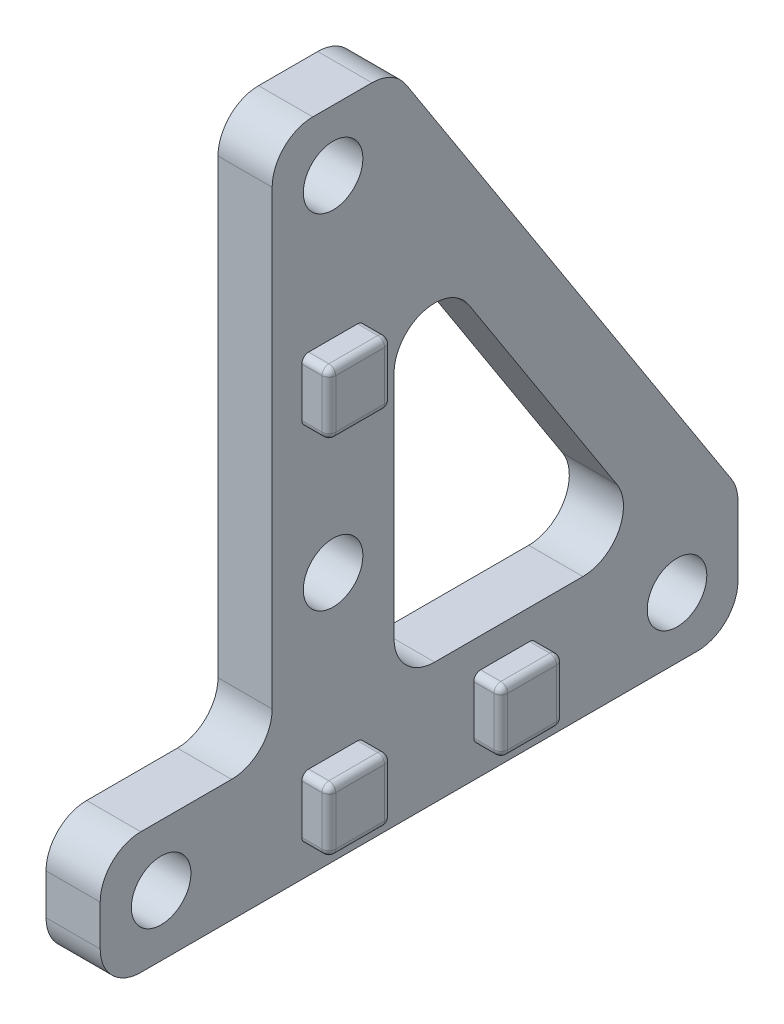
SolidWorks part; units mm, degrees
ref_plane "Front Plane" through (0, 0, 0) normal (0, 0, 1) x (1, 0, 0)
ref_plane "Top Plane" through (0, 0, 0) normal (0, 1, 0) x (1, 0, 0)
ref_plane "Right Plane" through (0, 0, 0) normal (1, 0, 0) x (0, 0, -1)
sketch "Sketch1" plane through (0, 0, 0) normal (1, 0, 0) x (0, 0, -1)
  line L0 (-4.5, 4.5) -> (-17.2, 4.5)
  line L1 (-17.2, 4.5) -> (-17.2, -4.5)
  line L2 (-17.2, -4.5) -> (29.9, -4.5)
  line L3 (29.9, -4.5) -> (29.9, 4.5)
  line L4 (29.9, 4.5) -> (4.5, 43.87)
  line L5 (4.5, 43.87) -> (-4.5, 43.87)
  line L6 (-4.5, 43.87) -> (-4.5, 4.5)
  line L7 (4.5, 4.5) -> (23.9497, 4.5)
  line L8 (23.9497, 4.5) -> (4.5, 34.6471)
  line L9 (4.5, 34.6471) -> (4.5, 4.5)
  circle A1 centre (25.4, 0) radius 2.2
  circle A2 centre (0, 13.97) radius 2.2
  circle A3 centre (0, 39.37) radius 2.2
  circle A4 centre (-12.7, 0) radius 2.2
  dimension "D1" = 4.4
  dimension "D2" = 12.7
  dimension "D3" = 25.4
  dimension "D4" = 13.97
  dimension "D5" = 25.4
  dimension "D6" = 4.5
  dimension "D7" = 4.5
  dimension "D8" = 4.5
  dimension "D9" = 9
  dimension "D10" = 4.5
  dimension "D11" = 4.5
  dimension "D12" = 9
  dimension "D13" = 9
  dimension "D14" = 5
extrude "Boss-Extrude1" add sketch "Sketch1" along normal blind 4
fillet "Fillet1" radius 3 10 edges at (2, 4.5, 4.5) (2, -4.5, 17.2) (2, 4.5, 17.2) (2, -4.5, -29.9) (2, 4.5, -29.9) (2, 43.87, -4.5) (2, 43.87, 4.5) (2, 4.5, -4.5) (2, 4.5, -23.9497) (2, 34.6471, -4.5)
sketch "Sketch2" plane through (4, 0, 0) normal (1, 0, 0) x (0, 0, -1)
  line L1 (2.3114, 2.3114) -> (-2.3114, 2.3114)
  line L2 (2.3114, 2.3114) -> (2.3114, -2.3114)
  line L3 (2.3114, -2.3114) -> (-2.3114, -2.3114)
  line L4 (-2.3114, 2.3114) -> (-2.3114, -2.3114)
  line L5 (2.3114, 2.3114) -> (-2.3114, -2.3114) construction
  line L6 (2.3114, -2.3114) -> (-2.3114, 2.3114) construction
  line L7 (15.0114, 2.3114) -> (10.3886, 2.3114)
  line L8 (15.0114, 2.3114) -> (15.0114, -2.3114)
  line L9 (15.0114, -2.3114) -> (10.3886, -2.3114)
  line L10 (10.3886, 2.3114) -> (10.3886, -2.3114)
  line L11 (15.0114, 2.3114) -> (10.3886, -2.3114) construction
  line L12 (15.0114, -2.3114) -> (10.3886, 2.3114) construction
  line L13 (-2.3114, 28.9814) -> (2.3114, 28.9814)
  line L14 (-2.3114, 28.9814) -> (-2.3114, 24.3586)
  line L15 (-2.3114, 24.3586) -> (2.3114, 24.3586)
  line L16 (2.3114, 28.9814) -> (2.3114, 24.3586)
  line L17 (-2.3114, 28.9814) -> (2.3114, 24.3586) construction
  line L18 (-2.3114, 24.3586) -> (2.3114, 28.9814) construction
  point P0 (0, 0)
  point P6 (12.7, 0)
  point P11 (0, 26.67)
  point P16 (0, 13.97)
  dimension "D1" = 12.7
  dimension "D2" = 12.7
  dimension "D3" = 4.6228
extrude "Boss-Extrude2" add sketch "Sketch2" along normal blind 2
fillet "Fillet2" radius 0.508 12 edges at (5, 2.3114, -15.0114) (5, 2.3114, -10.3886) (5, -2.3114, -10.3886) (5, -2.3114, -15.0114) (5, -2.3114, -2.3114) (5, 2.3114, -2.3114) (5, 2.3114, 2.3114) (5, -2.3114, 2.3114) (5, 28.9814, 2.3114) (5, 28.9814, -2.3114) (5, 24.3586, -2.3114) (5, 24.3586, 2.3114)
fillet "Fillet3" radius 0.508 24 edges at (6, -2.1626, -10.5374) (6, 0, -10.3886) (6, 2.1626, -10.5374) (6, 2.3114, -12.7) (6, 2.1626, -14.8626) (6, 0, -15.0114) (6, -2.1626, -14.8626) (6, -2.1626, 2.1626) (6, 0, 2.3114) (6, 2.1626, 2.1626) (6, 2.3114, 0) (6, 2.1626, -2.1626) (6, 0, -2.3114) (6, -2.1626, -2.1626) (6, 24.5074, 2.1626) (6, 26.67, 2.3114) (6, 28.8326, 2.1626) (6, 28.9814, 0) (6, 28.8326, -2.1626) (6, 26.67, -2.3114) (6, 24.5074, -2.1626) (6, -2.3114, -12.7) (6, -2.3114, 0) (6, 24.3586, 0)
